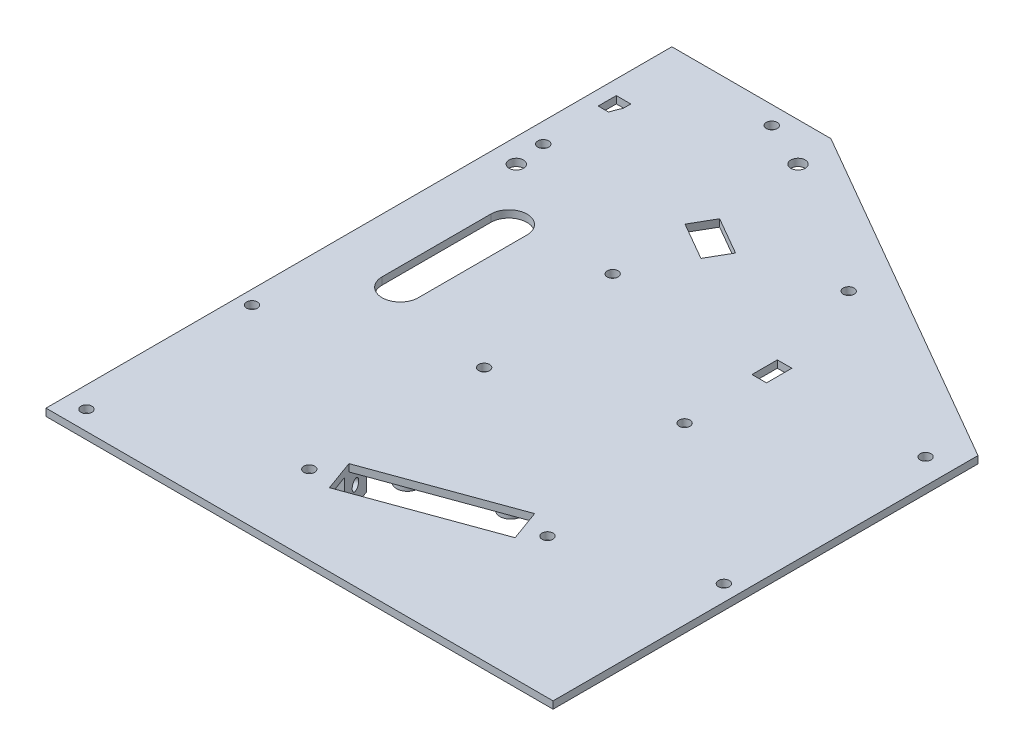
SolidWorks part; units mm, degrees
ref_plane "Front Plane" through (0, 0, 0) normal (0, 0, 1) x (1, 0, 0)
ref_plane "Top Plane" through (0, 0, 0) normal (0, 1, 0) x (1, 0, 0)
ref_plane "Right Plane" through (0, 0, 0) normal (1, 0, 0) x (0, 0, -1)
sketch "Sketch1" plane through (0, 0, 0) normal (0, 1, 0) x (1, 0, 0)
  line L1 (-70, 100) -> (70, 100)
  line L2 (-70, 100) -> (-70, -100)
  line L3 (-70, -100) -> (70, -100)
  line L4 (70, 100) -> (70, -100)
  line L5 (-70, 100) -> (70, -100) construction
  line L6 (-70, -100) -> (70, 100) construction
  point P0 (0, 0)
  dimension "D1" = 200
  dimension "D2" = 140
extrude "Boss-Extrude1" add sketch "Sketch1" along normal blind 2
sketch "Sketch2" plane through (0, 2, 0) normal (0, 1, 0) x (1, 0, 0)
  line L0 (-60, 63) -> (30, 11.0385) construction
  line L1 (-70, 100) -> (-70, -100) construction
  line L2 (70, -14.4027) -> (23.0154, -31.5037) construction
  line L3 (70, -100) -> (70, 100) construction
  line L4 (-50.6218, 98) -> (-70, 98) construction
  line L5 (-60, 63) -> (-50.6218, 63) construction
  line L6 (70, 100) -> (-70, 100) construction
  line L7 (70, -14.4027) -> (47.7176, -14.4027) construction
  line L8 (-51.25, 78.1554) -> (38.75, 26.1939) construction
  line L9 (-60, 63) -> (-70, 63) construction
  line L10 (-50.6218, 98) -> (70, 28.359) construction
  line L11 (-25.7823, 59.4102) -> (-22.2823, 65.4724)
  line L12 (-25.7823, 59.4102) -> (-15.39, 53.4102)
  line L13 (-22.2823, 65.4724) -> (-11.89, 59.4724)
  line L14 (-15.39, 53.4102) -> (-11.89, 59.4724)
  line L15 (-25.7823, 59.4102) -> (-11.89, 59.4724)
  line L16 (-51.25, 78.1554) -> (-70, 78.1554) construction
  line L17 (-50.6218, 98) -> (47.5, 41.3494) construction
  line L18 (-66, 80.6554) -> (-62, 80.6554)
  line L19 (-66, 80.6554) -> (-66, 75.6554)
  line L20 (-66, 75.6554) -> (-62, 75.6554)
  line L21 (-62, 80.6554) -> (-62, 75.6554)
  line L22 (-66, 80.6554) -> (-62, 75.6554) construction
  line L23 (-66, 75.6554) -> (-62, 80.6554) construction
  line L24 (19.4272, 32.69) -> (23.4317, 32.69)
  line L25 (19.4272, 32.69) -> (19.4272, 39.6978)
  line L26 (19.4272, 39.6978) -> (23.4317, 39.6978)
  line L27 (23.4317, 32.69) -> (23.4317, 39.6978)
  line L28 (19.4272, 32.69) -> (23.4317, 39.6978) construction
  line L29 (19.4272, 39.6978) -> (23.4317, 32.69) construction
  line L30 (30, 11.0385) -> (30, -28.9615) construction
  line L31 (-70, -65.3585) -> (-14.5723, -45.1845) construction
  line L32 (30, 11.0385) -> (-70, -25.3585) construction
  circle A0 centre (-43.9688, 69.9102) radius 20
  point P10 (-18.8361, 59.4413)
  point P13 (-64, 78.1554)
  point P25 (-64, 75.6554)
  point P26 (21.4295, 36.1939)
  point P37 (0, 0)
  point P43 (0, 0)
  point P44 (-43.758, 70.1013)
  dimension "D6" = 40
  dimension "D1" = 37
  dimension "D2" = 30
  dimension "D3" = 20
  dimension "D4" = 40
  dimension "D5" = 10
  dimension "D9" = 11
  dimension "D10" = 5
  dimension "D11" = 4
  dimension "D12" = 4
  dimension "D13" = 12
  dimension "D14" = 7
  dimension "D15" = 20
  dimension "D16" = 40
  dimension "D17" = 50
  dimension "D18" = 40
  dimension "D19" = 21
  dimension "D20" = 3.5
  dimension "D7" = 35
  dimension "D8" = 17.5
sketch "Sketch3" plane through (0, 2, 0) normal (0, 1, 0) x (1, 0, 0)
  line L0 (-50.6218, 98) -> (70, 28.359) construction
  line L1 (-60, 63) -> (30, 11.0385) construction
  line L2 (30, 11.0385) -> (-70, -25.3585) construction
  line L3 (70, -14.4027) -> (23.0154, -31.5037) construction
  line L4 (-70, -65.3585) -> (-14.5723, -45.1845) construction
  line L5 (-50.6218, 98) -> (70, 28.359)
  line L6 (-60, 63) -> (30, 11.0385)
  line L7 (30, 11.0385) -> (-70, -25.3585)
  line L8 (70, -14.4027) -> (23.0154, -31.5037)
  line L9 (-70, -65.3585) -> (-14.5723, -45.1845)
  line L10 (-60, 63) -> (-70, 63) construction
  line L11 (-60, 63) -> (-70, 63)
extrude "Cut-Extrude-Thin1" [suppressed] cut sketch "Sketch3" against normal blind 0.5 thin contours L11 L6 L7 thin type one direction wall 2.5
sketch "Sketch4" plane through (0, 0, 0) normal (0, -1, 0) x (1, 0, 0)
  circle A0 centre (-43.9688, -69.9102) radius 20 construction
  circle A1 centre (-43.9688, -69.9102) radius 20
extrude "Cut-Extrude1" cut sketch "Sketch4" against normal blind 1
sketch "Sketch6" plane through (0, 0, 0) normal (0, -1, 0) x (1, 0, 0)
  line L0 (-24.5234, -89.3556) -> (-63.4142, -50.4648) construction
  line L1 (-25.9376, -90.7698) -> (-64.8285, -51.879) construction
  line L2 (-23.1092, -87.9414) -> (-62, -49.0505) construction
  line L4 (-51.25, -78.1554) -> (38.75, -26.1939) construction
  arc A0 (-25.9376, -90.7698) -> (-23.1092, -87.9414) centre (-24.5234, -89.3556) ccw construction
  arc A1 (-62, -49.0505) -> (-64.8285, -51.879) centre (-63.4142, -50.4648) ccw construction
  circle A2 centre (-63.4142, -50.4648) radius 2
  circle A3 centre (-24.5234, -89.3556) radius 2
  point P2 (-43.9688, -69.9102)
  dimension "D1" = 55
  dimension "D2" = 4
  dimension "D3" = 105
extrude "Cut-Extrude2" cut sketch "Sketch6" against normal up to next
extrude "Cut-Extrude4" cut sketch "Sketch2" against normal through all and the other way through all contours L15 L12 L14 | L11 L15 L13 | L21 L18 L19 L20 | L24 L27 L26 L25 region at (-17.6874, 2, -57.4309) region at (-19.9848, 2, -61.4516) region at (-64.1556, 2, -78.3) region at (21.4295, 2, -36.1939)
sketch "Sketch7" plane through (0, 2, 0) normal (0, 1, 0) x (1, 0, 0)
  line L0 (-14.5723, -45.1845) -> (23.0154, -31.5037)
  line L1 (23.0154, -31.5037) -> (25.7515, -39.0213)
  line L2 (25.7515, -39.0213) -> (-11.8362, -52.7021)
  line L3 (-11.8362, -52.7021) -> (-14.5723, -45.1845)
  line L4 (-14.5723, -45.1845) -> (23.0154, -31.5037)
  line L5 (-14.5723, -45.1845) -> (-14.9144, -44.2448)
  line L6 (23.0154, -31.5037) -> (22.6733, -30.564)
  line L7 (-14.9144, -44.2448) -> (22.6733, -30.564)
  line L8 (70, -14.4027) -> (23.0154, -31.5037) construction
  dimension "D1" = 8
  dimension "D2" = 40
  dimension "D3" = 1
extrude "Cut-Extrude5" cut sketch "Sketch7" against normal up to surface (2 mm away) contours L3 L2 L1 L0 | L7 L5 L0 L6 region at (4.0505, 2, 37.8743) region at (5.5896, 2, 42.1029) up to face at (21.4295, 0, -36.1939)
sketch "Sketch8" plane through (10.198, 0, -3.7118) normal (-0.9397, 0, 0.342) x (0.342, 0, 0.9397)
  line L1 (38.4755, 0) -> (28.4755, 0)
  line L2 (38.4755, 0) -> (38.4755, -10)
  line L3 (38.4755, -10) -> (28.4755, -10)
  line L4 (28.4755, 0) -> (28.4755, -10)
  line L5 (117.9107, 0) -> (-70.0279, 0) construction
  circle A0 centre (33.4755, -5) radius 1.5
  point P9 (28.4755, -5)
  point P11 (33.4755, -10)
  dimension "D3" = 3
  dimension "D1" = 10
  dimension "D2" = 10
  dimension "D4" = 2
extrude "Boss-Extrude2" add sketch "Sketch8" against normal blind 4
ref_plane "Plane1" through (-8.5959, 0, 3.1286) normal (-0.9397, 0, 0.342) x (0.342, 0, 0.9397)
mirror "Mirror1" about plane through (-8.5959, 0, 3.1286) normal (-0.9397, 0, 0.342) of "Boss-Extrude2"
sketch "Sketch9" plane through (0, 0, 0) normal (0, -1, 0) x (-1, 0, 0)
  line L5 (15.4671, -16.7774) -> (9.3107, -33.6919) construction
  line L6 (16.4068, -17.1194) -> (10.2504, -34.0339)
  line L7 (14.5274, -16.4354) -> (8.3711, -33.3498)
  line L8 (-22.6733, -30.564) -> (14.9144, -44.2448) construction
  line L9 (17.6505, -36.7273) -> (14.2303, -46.1242) construction
  line L10 (18.2862, -17.8035) -> (12.1298, -34.7179)
  line L11 (12.648, -15.7513) -> (6.4917, -32.6658)
  arc A0 (16.4068, -17.1194) -> (14.5274, -16.4354) centre (15.4671, -16.7774) ccw
  arc A1 (8.3711, -33.3498) -> (10.2504, -34.0339) centre (9.3107, -33.6919) ccw
  arc A2 (6.4917, -32.6658) -> (12.1298, -34.7179) centre (9.3107, -33.6919) ccw
  arc A3 (18.2862, -17.8035) -> (12.648, -15.7513) centre (15.4671, -16.7774) ccw
  point P7 (12.3889, -25.2346)
  dimension "D5" = 1
  dimension "D1" = 8
  dimension "D2" = 7.875
  dimension "D3" = 2
  dimension "D7" = 18
extrude "Boss-Extrude4" add sketch "Sketch9" along normal blind 5
mirror "Mirror2" about plane through (-8.5959, 0, 3.1286) normal (-0.9397, 0, 0.342) of "Boss-Extrude4"
sketch "Sketch10" plane through (0, 0, 0) normal (0, -1, 0) x (1, 0, 0)
  line L0 (-29.3313, -56.2631) -> (-26.7332, -54.7631)
  line L1 (-29.3313, -56.2631) -> (-32.0813, -51.4999)
  line L2 (-26.7332, -54.7631) -> (-29.4832, -49.9999)
  line L3 (-32.0813, -51.4999) -> (-29.4832, -49.9999)
  line L4 (-25.7823, -59.4102) -> (-15.39, -53.4102) construction
  line L6 (-25.7823, -59.4102) -> (-22.2823, -65.4724) construction
  dimension "D1" = 4.5
  dimension "D2" = 5.5
  dimension "D3" = 3
  dimension "D4" = 1.5
extrude "Boss-Extrude5" add sketch "Sketch10" along normal blind 23
sketch "Sketch11" plane through (-46.3611, 0, -26.7666) normal (-0.866, 0, -0.5) x (-0.5, 0, 0.866)
  line L0 (-31.5596, -20.0043) -> (-31.5596, -16.0043) construction
  line L1 (-32.5596, -20.0043) -> (-32.5596, -16.0043)
  line L2 (-30.5596, -20.0043) -> (-30.5596, -16.0043)
  line L3 (-28.5596, -23) -> (-34.0596, -23) construction
  line L4 (-28.5596, -23) -> (-28.5596, 0) construction
  line L5 (-31.5596, -6.5043) -> (-31.5596, -2.5043) construction
  line L6 (-32.5596, -6.5043) -> (-32.5596, -2.5043)
  line L7 (-30.5596, -6.5043) -> (-30.5596, -2.5043)
  arc A0 (-32.5596, -20.0043) -> (-30.5596, -20.0043) centre (-31.5596, -20.0043) ccw
  arc A1 (-30.5596, -16.0043) -> (-32.5596, -16.0043) centre (-31.5596, -16.0043) ccw
  arc A2 (-32.5596, -6.5043) -> (-30.5596, -6.5043) centre (-31.5596, -6.5043) ccw
  arc A3 (-30.5596, -2.5043) -> (-32.5596, -2.5043) centre (-31.5596, -2.5043) ccw
  point P3 (-31.5596, -18.0043)
  point P19 (-31.5596, -4.5043)
  dimension "D1" = 2.9957
  dimension "D2" = 4
  dimension "D3" = 3
  dimension "D4" = 2
  dimension "D5" = 13.5
extrude "Cut-Extrude6" cut sketch "Sketch11" against normal up to next
ref_plane "Plane2" through (21.0298, 0, -36.4247) normal (-0.5, 0, 0.866) x (0.866, 0, 0.5)
mirror "Mirror3" about plane through (21.0298, 0, -36.4247) normal (-0.5, 0, 0.866) of "Cut-Extrude6", "Boss-Extrude5"
hole_wizard "Ø3.0mm Clearance Dowel Hole1" positions "Sketch14" profile "Sketch15" hole size "Ø3.0" standard "ANSI Metric" end condition through all
sketch "Sketch14" plane through (-89.742, 2, 119.4997) normal (0, 1, 0) x (1, 0, 0)
  point P0 (23.5423, 99.781)
  point P1 (25.5944, 52.0145)
  point P2 (70.6996, 68.4315)
  point P3 (70.5269, 116.8821)
  point P4 (111.4918, 131.26)
  point P5 (119.5864, 85.3143)
  point P6 (155.2948, 98.311)
  point P7 (152.8064, 156.4818)
  point P8 (65.8782, 157.0177)
  point P9 (102.577, 185.4818)
  point P10 (52.3475, 214.4818)
  point P11 (25.242, 178.4997)
sketch "Sketch15" plane through (-66.1998, 2, 19.7187) normal (1, 0, 0) x (0, 0, 1)
  line L0 (0, 0) -> (0, 25)
  line L1 (0, 25) -> (1.5, 25)
  line L2 (1.5, 25) -> (1.5, 0)
  line L3 (1.5, 0) -> (0, 0)
  line L4 (0, -6.35) -> (0, 107.95) construction
  dimension "Thru Hole Dia." = 3
  dimension "Thru Hole Depth" = 25
sketch "Sketch16" plane through (0, 2, 0) normal (0, 1, 0) x (1, 0, 0)
  line L1 (-43.6218, 110.1244) -> (83.0261, 110.1244)
  line L2 (-43.6218, 110.1244) -> (77, 40.4833)
  line L3 (-43.6218, 110.1244) -> (77, 40.4833)
  line L4 (83.0261, 110.1244) -> (83.0261, 36.9032)
  line L5 (83.0261, 36.9032) -> (77, 40.4833)
  dimension "D1" = 14
extrude "Cut-Extrude7" cut sketch "Sketch16" against normal through all
sketch "Sketch17" plane through (0, 2, 0) normal (0, 1, 0) x (1, 0, 0)
  line L0 (-43.2303, 98) -> (-26.6218, 98)
  line L1 (-26.6218, 98) -> (68, 43.3701)
  line L2 (68, 43.3701) -> (68, 33.0364)
  line L3 (70, -100) -> (70, 44.5248) construction
  line L4 (-26.0859, 100) -> (70, 44.5248) construction
  line L5 (-26.0859, 100) -> (-70, 100) construction
  line L6 (-43.2303, 98) -> (-46.6944, 100)
  line L7 (-46.6944, 100) -> (-26.0859, 100)
  line L8 (-26.0859, 100) -> (70, 44.5248)
  line L9 (70, 44.5248) -> (70, 31.875)
  line L10 (70, 31.875) -> (68, 33.0364)
  dimension "D1" = 2
  dimension "D2" = 2
  dimension "D3" = 2
extrude "Boss-Extrude6" [suppressed] add sketch "Sketch17" along normal blind 4
sketch "Sketch18" plane through (0, 2, 0) normal (0, 1, 0) x (1, 0, 0)
  line L0 (-70, 100) -> (-70, -100) construction
  line L1 (-70, -72.7995) -> (70, -72.7995)
  line L2 (-70, -72.7995) -> (-70, -100)
  line L3 (-70, -100) -> (70, -100)
  line L4 (70, -72.7995) -> (70, -100)
extrude "Cut-Extrude8" cut sketch "Sketch18" against normal through all
extrude "Cut-Extrude9" cut sketch "Sketch19" against normal through all
sketch "Sketch19" plane through (-89.742, 8, 119.4997) normal (0, 1, 0) x (1, 0, 0)
  line L0 (39.742, 154.4997) -> (39.742, 124.4997) construction
  line L1 (44.742, 154.4997) -> (44.742, 124.4997)
  line L2 (34.742, 154.4997) -> (34.742, 124.4997)
  arc A0 (44.742, 154.4997) -> (34.742, 154.4997) centre (39.742, 154.4997) ccw
  arc A1 (34.742, 124.4997) -> (44.742, 124.4997) centre (39.742, 124.4997) ccw
  point P2 (39.742, 139.4997)
  point P9 (0, 0)
